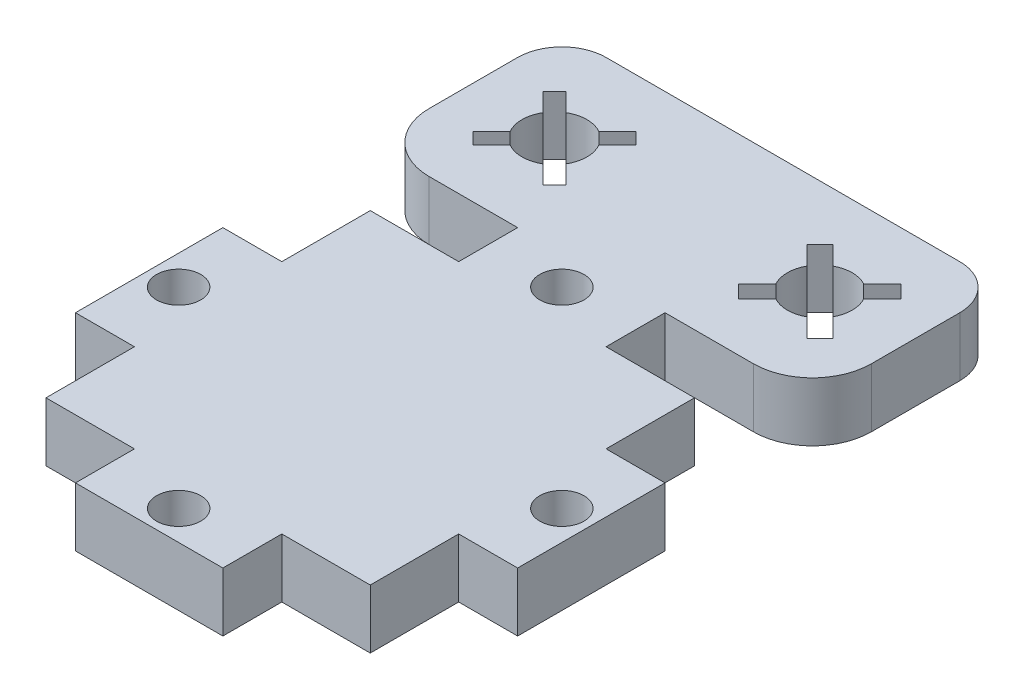
SolidWorks part; units mm, degrees
ref_plane "Front Plane" through (0, 0, 0) normal (0, 0, 1) x (1, 0, 0)
ref_plane "Top Plane" through (0, 0, 0) normal (0, 1, 0) x (1, 0, 0)
ref_plane "Right Plane" through (0, 0, 0) normal (1, 0, 0) x (0, 0, -1)
sketch "Sketch1" plane through (0, 0, 0) normal (0, 1, 0) x (1, 0, 0)
  line L1 (0, 0) -> (30, 0)
  line L2 (0, 0) -> (0, 30)
  line L3 (0, 30) -> (30, 30)
  line L4 (30, 0) -> (30, 30)
  line L9 (0, 30) -> (4, 30)
  line L10 (0, 30) -> (0, 0)
  line L11 (0, 0) -> (4, 0)
  line L12 (4, 30) -> (4, 0)
  line L13 (0, 0) -> (30, 0)
  line L14 (0, 0) -> (0, 4)
  line L15 (0, 4) -> (30, 4)
  line L16 (30, 0) -> (30, 4)
  line L17 (30, 0) -> (26, 0)
  line L18 (30, 0) -> (30, 30)
  line L19 (30, 30) -> (26, 30)
  line L20 (26, 0) -> (26, 30)
  line L21 (30, 30) -> (0, 30)
  line L22 (30, 30) -> (30, 26)
  line L23 (30, 26) -> (0, 26)
  line L24 (0, 30) -> (0, 26)
  line L25 (0, 20) -> (4, 20)
  line L26 (0, 20) -> (0, 10)
  line L27 (0, 10) -> (4, 10)
  line L28 (4, 20) -> (4, 10)
  line L29 (10, 26) -> (20, 26)
  line L30 (10, 26) -> (10, 30)
  line L31 (10, 30) -> (20, 30)
  line L32 (20, 26) -> (20, 30)
  line L33 (26, 20) -> (30, 20)
  line L34 (26, 20) -> (26, 10)
  line L35 (26, 10) -> (30, 10)
  line L36 (30, 20) -> (30, 10)
  line L37 (20, 4) -> (10, 4)
  line L38 (20, 4) -> (20, 0)
  line L39 (20, 0) -> (10, 0)
  line L40 (10, 4) -> (10, 0)
  point P29 (10, 2)
  dimension "D1" = 30
  dimension "D2" = 30
  dimension "D3" = 4
  dimension "D4" = 4
  dimension "D5" = 4
  dimension "D6" = 4
  dimension "D7" = 10
  dimension "D8" = 10
  dimension "D9" = 10
  dimension "D10" = 10
  dimension "D11" = 10
  dimension "D12" = 10
  dimension "D13" = 10
  dimension "D14" = 10
extrude "Boss-Extrude1" add sketch "Sketch1" along normal blind 4 contours L20 L23 L12 L15 | L15 L40 L13 L38 | L20 L35 L18 L33 | L23 L32 L21 L30 | L2 L27 L12 L25 region at (15, 0, -2) region at (15, 0, -15) region at (2, 0, -15) region at (28, 0, -15) region at (15, 0, -28)
sketch "Sketch3" plane through (0, 0, -30) normal (0, 0, -1) x (-1, 0, 0)
  line L1 (-30, 4) -> (0, 4)
  line L2 (-30, 4) -> (-30, 0)
  line L3 (-30, 0) -> (0, 0)
  line L4 (0, 4) -> (0, 0)
  dimension "D1" = 4
  dimension "D2" = 30
extrude "Boss-Extrude2" add sketch "Sketch3" along normal blind 13
sketch "Sketch4" plane through (0, 4, 0) normal (0, 1, 0) x (1, 0, 0)
  line L0 (15, 0) -> (15, 54.4346) construction
  line L1 (10, 0) -> (20, 0) construction
  line L2 (30, 36.5) -> (0, 36.5) construction
  line L3 (30, 43) -> (30, 30) construction
  line L4 (0, 43) -> (0, 30) construction
  line L5 (9.1466, 38.8688) -> (3.6312, 33.3534)
  line L10 (21.6842, 39.6997) -> (27.1997, 34.1842)
  line L11 (21.6842, 39.6997) -> (20.8003, 38.8158)
  line L12 (9.1466, 38.8688) -> (8.3688, 39.6466)
  line L13 (3.6312, 33.3534) -> (2.8534, 34.1312)
  line L14 (8.3688, 39.6466) -> (2.8534, 34.1312)
  line L15 (9.1466, 38.8688) -> (2.8534, 34.1312) construction
  line L16 (3.6312, 33.3534) -> (8.3688, 39.6466) construction
  line L17 (27.1997, 34.1842) -> (26.3158, 33.3003)
  line L18 (20.8003, 38.8158) -> (26.3158, 33.3003)
  line L19 (21.6842, 39.6997) -> (26.3158, 33.3003) construction
  line L20 (27.1997, 34.1842) -> (20.8003, 38.8158) construction
  line L21 (6, 36.5) -> (6, 32.0849) construction
  line L23 (8.3688, 33.3534) -> (9.1466, 34.1312)
  line L24 (3.6312, 39.6466) -> (9.1466, 34.1312)
  line L25 (2.8534, 38.8688) -> (3.6312, 39.6466)
  line L26 (2.8534, 38.8688) -> (8.3688, 33.3534)
  line L27 (24, 36.5) -> (24, 50.8012) construction
  line L28 (20.8003, 34.1842) -> (21.6842, 33.3003)
  line L29 (27.1997, 38.8158) -> (21.6842, 33.3003)
  line L30 (26.3158, 39.6997) -> (27.1997, 38.8158)
  line L31 (26.3158, 39.6997) -> (20.8003, 34.1842)
  circle A0 centre (24, 36.5) radius 2.2
  circle A1 centre (6, 36.5) radius 2.2
  dimension "D1" = 4.4
  dimension "D3" = 4.4
  dimension "D6" = 1.25
  dimension "D7" = 7.8
  dimension "D8" = 1.1
  dimension "D9" = 7.8
  dimension "D10" = 45
  dimension "D11" = 45
extrude "Cut-Extrude2" cut sketch "Sketch4" against normal blind 10 contours A1 L24 L25 L26 | A1 L14 L13 L5 | A1 L26 L23 L24 | A1 L5 L12 L14 | A1 | L10 L11 L18 L17 | L28 L29 L30 L31 | A0 region at (8.1484, 4, -38.6484) region at (8.1484, 4, -34.3516) region at (3.8516, 4, -38.6484) region at (3.8516, 4, -34.3516)
fillet "Fillet1" radius 3 2 edges at (0, 2, -43) (30, 2, -43)
fillet "Fillet2" radius 4 2 edges at (0, 2, -30) (30, 2, -30)
sketch "Sketch6" plane through (0, 4, 0) normal (0, 1, 0) x (1, 0, 0)
  line L0 (20, 2) -> (10, 2) construction
  line L1 (20, 4) -> (20, 0) construction
  line L2 (10, 4) -> (10, 0) construction
  line L3 (28, 20) -> (28, 10) construction
  line L4 (26, 20) -> (30, 20) construction
  line L5 (26, 10) -> (30, 10) construction
  line L6 (20, 28) -> (10, 28) construction
  line L7 (20, 26) -> (20, 30) construction
  line L8 (10, 26) -> (10, 30) construction
  line L9 (2, 20) -> (2, 10) construction
  line L10 (0, 20) -> (4, 20) construction
  line L11 (0, 10) -> (4, 10) construction
  line L12 (30, 15) -> (0, 15) construction
  line L13 (30, 10) -> (30, 20) construction
  line L14 (0, 10) -> (0, 20) construction
  line L15 (15, 30.55) -> (15, 0) construction
  line L16 (15.625, 30.55) -> (14.375, 30.55) construction
  line L17 (10, 0) -> (20, 0) construction
  circle A0 centre (28, 15) radius 1.5
  circle A1 centre (15, 2) radius 1.5
  circle A2 centre (2, 15) radius 1.5
  circle A3 centre (15, 28) radius 1.5
  dimension "D1" = 3
  dimension "D2" = 3
  dimension "D3" = 3
  dimension "D4" = 3
extrude "Cut-Extrude3" cut sketch "Sketch6" against normal blind 10
